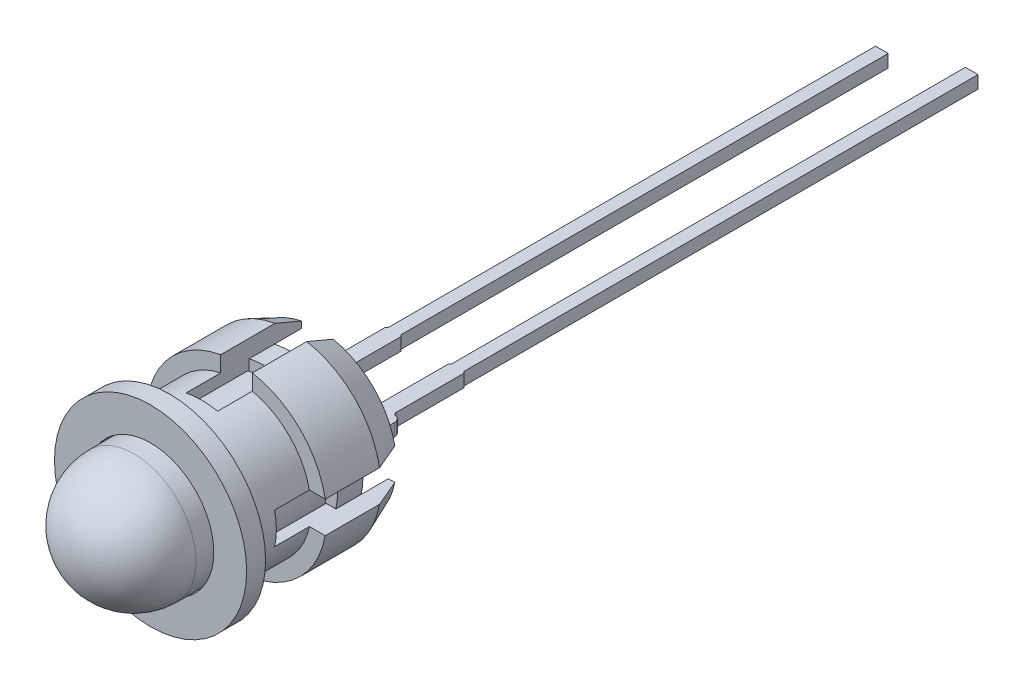
SolidWorks part; units mm, degrees
ref_plane "FRONT" through (0, 0, 0) normal (0, 0, 1) x (1, 0, 0)
ref_plane "TOP" through (0, 0, 0) normal (0, 1, 0) x (1, 0, 0)
ref_plane "RIGHT" through (0, 0, 0) normal (1, 0, 0) x (0, 0, -1)
sketch "Sketch1" plane through (0, 0, 0) normal (1, 0, 0) x (0, 0, -1)
  line L0 (-68.7324, 0) -> (61.468, 0) construction
  line L1 (0, 0) -> (0, 2.921)
  line L2 (0, 2.921) -> (-1.016, 2.921)
  line L3 (-1.016, 2.921) -> (-1.016, 2.5)
  line L4 (-1.016, 2.5) -> (-6.2884, 2.5)
  line L5 (0, 0) -> (-8.7884, 0)
  arc A0 (-6.2884, 2.5) -> (-8.7884, 0) centre (-6.2884, 0) ccw
  dimension "D1" = 5
  dimension "D2" = 8.7884
  dimension "D3" = 1.016
  dimension "D4" = 5.842
revolve "Revolve1" add sketch "Sketch1" angle 360 about L0
sketch "Sketch3" plane through (0, 0, 0) normal (0, 1, 0) x (1, 0, 0)
  line L0 (0, 3.1728) -> (0, -11.1239) construction
  line L2 (0.8382, 0) -> (1.7018, 0)
  line L3 (0.8382, 0) -> (0.8382, 1.741)
  line L4 (0.9525, 5.3975) -> (1.016, 5.461)
  line L5 (1.7018, 0) -> (1.7018, 1.741)
  line L6 (2.921, 0) -> (-2.921, 0) construction
  line L7 (-1.27, 0) -> (-1.27, 25.0444) construction
  line L8 (0.635, 2.2896) -> (0.635, 2.078)
  line L9 (-1.5875, 5.3975) -> (-1.524, 5.461)
  line L10 (1.905, 2.2896) -> (1.905, 2.078)
  line L11 (1.5875, 2.6652) -> (1.5875, 5.3975)
  line L12 (0.9525, 2.6652) -> (0.9525, 5.3975)
  line L13 (-1.524, 25.0444) -> (-1.016, 25.0444)
  line L14 (1.27, 0) -> (1.27, 26.1112) construction
  line L15 (-1.524, 5.461) -> (-1.524, 25.0444)
  line L16 (-1.016, 5.461) -> (-1.016, 25.0444)
  line L17 (1.016, 5.461) -> (1.016, 26.1112)
  line L18 (1.524, 5.461) -> (1.524, 26.1112)
  line L19 (1.524, 26.1112) -> (1.016, 26.1112)
  line L20 (1.5875, 5.3975) -> (1.524, 5.461)
  line L21 (-0.9525, 2.6652) -> (-0.9525, 5.3975)
  line L22 (-1.5875, 2.6652) -> (-1.5875, 5.3975)
  line L23 (-1.905, 2.2896) -> (-1.905, 2.078)
  line L24 (-0.635, 2.2896) -> (-0.635, 2.078)
  line L25 (-1.7018, 0) -> (-1.7018, 1.741)
  line L26 (-0.9525, 5.3975) -> (-1.016, 5.461)
  line L27 (-0.8382, 0) -> (-0.8382, 1.741)
  line L28 (-0.8382, 0) -> (-1.7018, 0)
  arc A0 (0.8467, 2.54) -> (0.635, 2.2896) centre (0.889, 2.2896) ccw
  arc A1 (1.905, 2.2896) -> (1.6933, 2.54) centre (1.651, 2.2896) ccw
  arc A2 (1.7695, 1.8533) -> (1.905, 2.078) centre (1.651, 2.078) ccw
  arc A3 (0.635, 2.078) -> (0.7705, 1.8533) centre (0.889, 2.078) ccw
  arc A4 (0.9525, 2.6652) -> (0.8467, 2.54) centre (0.8255, 2.6652) cw
  arc A5 (1.5875, 2.6652) -> (1.6933, 2.54) centre (1.7145, 2.6652) ccw
  arc A6 (1.7018, 1.741) -> (1.7695, 1.8533) centre (1.8288, 1.741) cw
  arc A7 (0.8382, 1.741) -> (0.7705, 1.8533) centre (0.7112, 1.741) ccw
  arc A8 (-0.8382, 1.741) -> (-0.7705, 1.8533) centre (-0.7112, 1.741) cw
  arc A9 (-1.7018, 1.741) -> (-1.7695, 1.8533) centre (-1.8288, 1.741) ccw
  arc A10 (-1.5875, 2.6652) -> (-1.6933, 2.54) centre (-1.7145, 2.6652) cw
  arc A11 (-0.9525, 2.6652) -> (-0.8467, 2.54) centre (-0.8255, 2.6652) ccw
  arc A12 (-0.635, 2.078) -> (-0.7705, 1.8533) centre (-0.889, 2.078) cw
  arc A13 (-1.7695, 1.8533) -> (-1.905, 2.078) centre (-1.651, 2.078) cw
  arc A14 (-1.905, 2.2896) -> (-1.6933, 2.54) centre (-1.651, 2.2896) cw
  arc A15 (-0.8467, 2.54) -> (-0.635, 2.2896) centre (-0.889, 2.2896) cw
  point P40 (1.5875, 2.54)
  dimension "D6" = 0.254
  dimension "D12" = 0.127
  dimension "D2" = 1.741
  dimension "D3" = 1.27
  dimension "D4" = 1.27
  dimension "D5" = 0.8636
  dimension "D7" = 45
  dimension "D8" = 0.635
  dimension "D9" = 0.508
  dimension "D10" = 26.1112
  dimension "D11" = 5.461
  dimension "D13" = 2.54
  dimension "D14" = 25.0444
  dimension "D15" = 0.508
extrude "Extrude1" add sketch "Sketch3" along normal blind 0.254 and the other way blind 0.254
sketch "Sketch4" plane through (0, 0, 0) normal (1, 0, 0) x (0, 0, -1)
  line L0 (-10.2232, 0) -> (15.2535, 0) construction
  line L1 (-5.6134, 2.54) -> (-5.6134, 3.8608)
  line L2 (-5.6134, 3.8608) -> (-4.8514, 3.8608)
  line L3 (-4.8514, 3.8608) -> (-4.8514, 2.9972)
  line L4 (-4.8514, 2.9972) -> (-2.159, 2.9972)
  line L5 (-2.159, 2.9972) -> (-2.159, 3.6195)
  line L6 (-2.159, 3.6195) -> (0.0254, 3.6195)
  line L7 (0.0254, 3.6195) -> (1.0922, 3.175)
  line L8 (1.0922, 3.175) -> (1.0922, 2.921)
  line L10 (-1.016, 2.54) -> (-5.6134, 2.54)
  line L11 (-1.016, 2.921) -> (-1.016, -2.921) construction
  line L12 (-1.016, 2.921) -> (-1.016, 2.54)
  line L13 (0, 2.921) -> (-1.016, 2.921) construction
  line L14 (1.0922, 2.921) -> (-1.016, 2.921)
  line L15 (-1.016, 0) -> (-1.016, -2.921)
  arc A0 (-6.2884, 2.5) -> (-6.2884, -2.5) centre (-6.2884, 0) ccw construction
  dimension "D7" = 3.175
  dimension "D1" = 0.762
  dimension "D2" = 2.6924
  dimension "D3" = 3.2512
  dimension "D4" = 7.239
  dimension "D5" = 5.9944
  dimension "D6" = 7.7216
  dimension "D8" = 6.35
  dimension "D9" = 2.1844
  dimension "D10" = 5.08
revolve "Revolve3" add sketch "Sketch4" angle 360 about L0 region at (0, 3.2004, 5.5451)
sketch "Sketch5" plane through (0, 0, 0) normal (0, 0, 1) x (1, 0, 0)
  line L1 (0, 4.3635) -> (0, -4.4967)
extrude "Cut-Extrude-Thin2" cut sketch "Sketch5" against normal through all and the other way blind 3.556 thin contours L1 thin type mid plane wall 1.27
pattern_circular "CirPattern2" count 2 over 90 about axis through (0, 0, 68.7324) along (0, 0, -1) of "Cut-Extrude-Thin2"
sketch "Sketch6" plane through (0, 0, 0) normal (1, 0, 0) x (0, 0, -1)
  line L0 (-9.9129, 0) -> (13.6637, 0) construction
  line L3 (-2.159, 4.572) -> (2.2098, 4.572)
  line L4 (-2.159, 4.572) -> (-2.159, 3.556)
  line L5 (-2.159, 3.556) -> (2.2098, 3.556)
  line L6 (2.2098, 4.572) -> (2.2098, 3.556)
  line L11 (-2.159, 3.5634) -> (-2.159, 0.635) construction
  dimension "D1" = 9.144
  dimension "D2" = 7.112
  dimension "D3" = 4.3688
